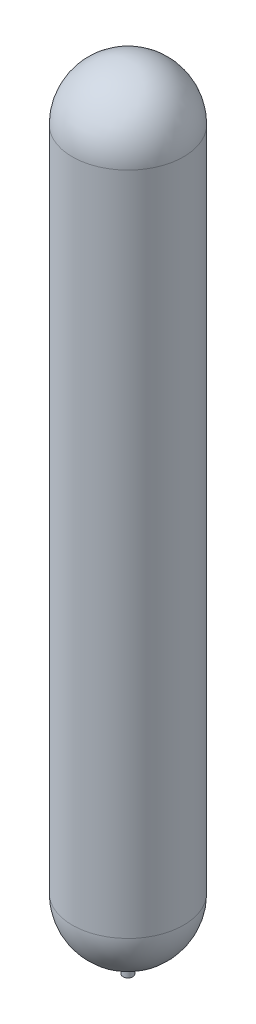
SolidWorks part; units mm, degrees
note: The reader was unsure of these and kept them because the rebuilt part matched: shared geometry of "Sketch1<4>".
ref_plane "Front Plane" through (0, 0, 0) normal (0, 0, 1) x (1, 0, 0)
ref_plane "Top Plane" through (0, 0, 0) normal (0, 1, 0) x (1, 0, 0)
ref_plane "Right Plane" through (0, 0, 0) normal (1, 0, 0) x (0, 0, -1)
sketch "Sketch1"
  line L0 (-114.7826, 1729.74) -> (-114.7826, 0)
  line L1 (-141.4526, 1729.74) -> (-141.4526, 0)
  line L2 (-144.78, 0) -> (-144.78, 1729.74)
  line L3 (0, 50.358) -> (0, -222.3667) construction
  line L6 (0, 1874.52) -> (0, 1871.1926)
  line L7 (0, 1844.5226) -> (0, 1871.1926)
  line L9 (-3.175, -182.3219) -> (-12.7, -182.3219)
  line L10 (-12.7, -182.3219) -> (-12.7, -140.8813)
  line L11 (-3.175, -114.7387) -> (-3.175, -182.3219)
  arc A0 (-114.7826, 1729.74) -> (0, 1844.5226) centre (0, 1729.74) cw
  arc A1 (-141.4526, 1729.74) -> (0, 1871.1926) centre (0, 1729.74) cw
  arc A2 (-144.78, 1729.74) -> (0, 1874.52) centre (0, 1729.74) cw
  arc A3 (-114.7826, 0) -> (-3.175, -114.7387) centre (0, 0) ccw
  arc A4 (-141.4526, 0) -> (-12.7, -140.8813) centre (0, 0) ccw
  arc A5 (-144.78, 0) -> (-12.7, -144.2219) centre (0, 0) ccw
  point P14 (-3.175, -130.6117)
  dimension "D5" = 144.78
  dimension "D4" = 1729.74
  dimension "D1" = 144.78
  dimension "D2" = 3.3274
  dimension "D3" = 26.67
  dimension "D7" = 9.525
  dimension "D8" = 38.1
  dimension "D6" = 15.873
  dimension "D9" = 3.175
sketch "Sketch1<4>" plane through (0, 0, 0) normal (0, 0, 1) x (1, 0, 0) same geometry as "Sketch1"
revolve "Revolve1" add sketch "Sketch1" angle 360 about L3
revolve "Revolve2" add sketch "Sketch1<4>" angle 360 about L3
equation "\"OD\" = 5.7'outside diameter"
equation "\"D1@Sketch1\"=\"OD\""
equation "\"t_wrap\"= 0.131'carbon fiber thickness"
equation "\"D2@Sketch1\"=\"t_wrap\""
equation "\"t_wall\" = 1.05'aluminum thickness"
equation "\"D3@Sketch1\"=\"t_wall\""
equation "\"D5@Sketch1\"=\"OD\""
